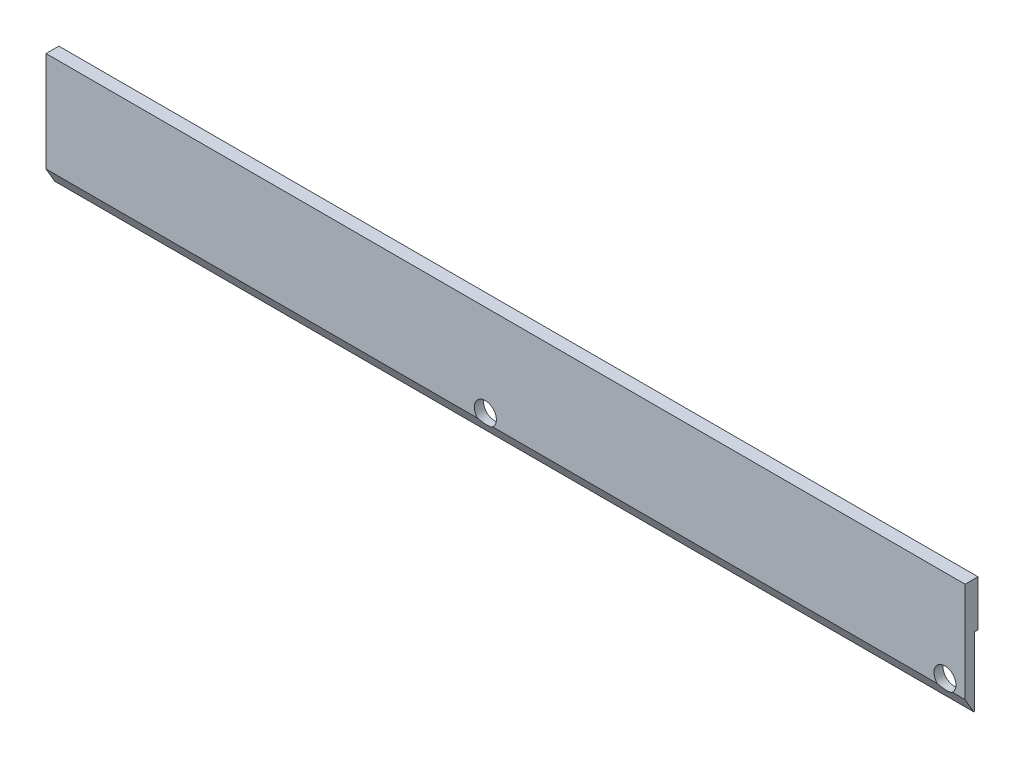
SolidWorks part; units mm, degrees
ref_plane "Front Plane" through (0, 0, 0) normal (0, 0, 1) x (1, 0, 0)
ref_plane "Top Plane" through (0, 0, 0) normal (0, 1, 0) x (1, 0, 0)
ref_plane "Right Plane" through (0, 0, 0) normal (1, 0, 0) x (0, 0, -1)
sketch "Sketch1" plane through (0, 0, 0) normal (0, 0, 1) x (1, 0, 0)
  line L0 (0, 0) -> (0, 38.5015) construction
  line L1 (0, 38.1) -> (254, 38.1)
  line L2 (0, 0) -> (127, 0) construction
  line L3 (0, 6.35) -> (254, 6.35)
  line L4 (0, 6.35) -> (0, 38.1)
  line L8 (254, 38.1) -> (254, 6.35)
  circle A0 centre (121.412, 12.7) radius 3.048
  circle A1 centre (248.412, 12.7) radius 3.048
  dimension "D1" = 6.35
  dimension "D2" = 31.75
extrude "Boss-Extrude1" add sketch "Sketch1" along normal blind 2.54 contours L0 L4 L3 L8 A1 A0 region at (126.5778, 22.2944, 0)
chamfer "Chamfer1" distance 2.38 angle 60 1 edges at (127, 6.35, 2.54) first distance on face at (127, 6.35, 1.27)
sketch "Sketch3" plane through (0, 0, 0) normal (0, 0, -1) x (-1, 0, 0)
  line L0 (0, 6.35) -> (0, 38.1) construction
  line L1 (-254, 38.1) -> (0, 38.1)
  line L2 (-254, 38.1) -> (-254, 25.4)
  line L3 (-254, 25.4) -> (0, 25.4)
  line L4 (0, 38.1) -> (0, 25.4)
  dimension "D1" = 12.7
extrude "Boss-Extrude2" add sketch "Sketch3" along normal blind 1.016
sketch "Sketch4" plane through (0, 0, 0) normal (0, 0, -1) x (-1, 0, 0)
  line L0 (0, 25.4) -> (0, 6.35)
  line L1 (0, 6.35) -> (-3.556, 6.35)
  line L2 (-14.224, 25.4) -> (0, 0) construction
  line L3 (0, 6.35) -> (-254, 6.35) construction
  line L4 (-3.556, 6.35) -> (-14.224, 25.4)
  line L5 (-254, 25.4) -> (0, 25.4) construction
  line L6 (-14.224, 25.4) -> (0, 25.4)
extrude "Boss-Extrude3" add sketch "Sketch4" along normal blind 1.016
